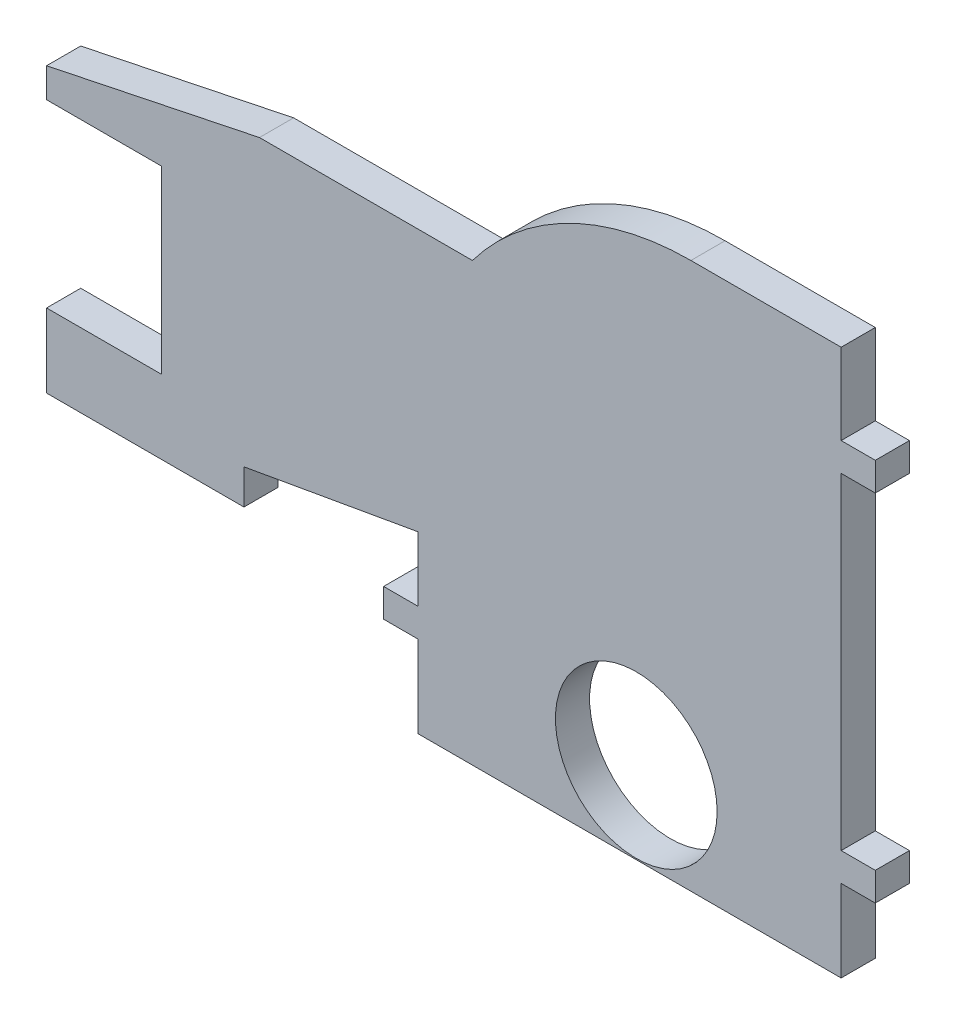
SolidWorks part; units mm, degrees
material "Balsa"
ref_plane "Front Plane" through (0, 0, 0) normal (0, 0, 1) x (1, 0, 0)
ref_plane "Top Plane" through (0, 0, 0) normal (0, 1, 0) x (1, 0, 0)
ref_plane "Right Plane" through (0, 0, 0) normal (1, 0, 0) x (0, 0, -1)
sketch "Sketch1" plane through (0, 0, 0) normal (0, 0, 1) x (1, 0, 0)
  line L0 (0, -1000.1535) -> (0, 48999.8465) construction
  line L1 (-7.62, 16.51) -> (-27.4189, 16.51)
  line L2 (-1000, 0) -> (49000, 0) construction
  line L3 (9.525, 16.51) -> (11.1125, 16.51)
  line L4 (2.54, 21.59) -> (9.525, 21.59)
  line L5 (-10.16, 8.89) -> (-10.16, -3.81)
  line L6 (-10.16, -3.81) -> (9.525, -3.81)
  line L7 (9.525, 21.59) -> (9.525, -3.81)
  line L8 (-11.7475, 0) -> (-10.16, 0)
  line L9 (-11.7475, 0) -> (-11.7475, 1.3208)
  line L10 (-11.7475, 1.3208) -> (-10.16, 1.3208)
  line L11 (-10.16, 0) -> (-10.16, 1.3208)
  line L12 (9.525, 0) -> (11.1125, 0)
  line L13 (9.525, 0) -> (9.525, 1.3208)
  line L14 (9.525, 1.3208) -> (11.1125, 1.3208)
  line L15 (11.1125, 0) -> (11.1125, 1.3208)
  line L16 (9.525, 16.51) -> (9.525, 17.8308)
  line L17 (9.525, 17.8308) -> (11.1125, 17.8308)
  line L18 (11.1125, 16.51) -> (11.1125, 17.8308)
  line L19 (-27.4189, 16.51) -> (-27.4189, 1.27)
  line L20 (-27.4189, 1.27) -> (-10.16, 4.318)
  line L21 (-27.4189, 13.081) -> (-22.0849, 13.081)
  line L22 (-22.0849, 13.081) -> (-22.0849, 4.699)
  line L23 (-22.0849, 4.699) -> (-27.4189, 4.699)
  line L24 (-27.4189, 1.27) -> (-18.2418, 1.27)
  line L25 (-18.2418, 1.27) -> (-18.2418, 2.8907)
  line L26 (-17.5195, 16.51) -> (-27.4189, 14.4526)
  circle A0 centre (0, 0) radius 3.7592
  arc A3 (2.54, 21.59) -> (-10.16, 8.89) centre (2.54, 8.89) ccw
  dimension "D1" = 7.5184
  dimension "D4" = 3.81
  dimension "D3" = 2.0574
  dimension "D9" = 12.7
  dimension "D10" = 1.5875
  dimension "D2" = 25.4
  dimension "D6" = 9.525
  dimension "D8" = 19.685
  dimension "D12" = 1.3208
  dimension "D13" = 1.3208
  dimension "D14" = 1.5875
  dimension "D15" = 2
extrude "Boss-Extrude1" add sketch "Sketch1" along normal blind 1.5875 contours L4 A3 L5 L6 L7 A0 | L10 L9 L8 L5 | L3 L18 L17 L7 | L12 L15 L14 L7 | A3 L1 L19 L20 L5 | L24 L25 L20 region at (-17.1775, 9.6272, 0) region at (0.225, 9.0166, 0) region at (10.3187, 17.1704, 0) region at (-10.9538, 0.6604, 0) region at (-21.3008, 1.8102, 0) region at (10.3187, 0.6604, 0)
move or copy body "Body-Move/Copy1" [suppressed] bodies to move or copy 101
